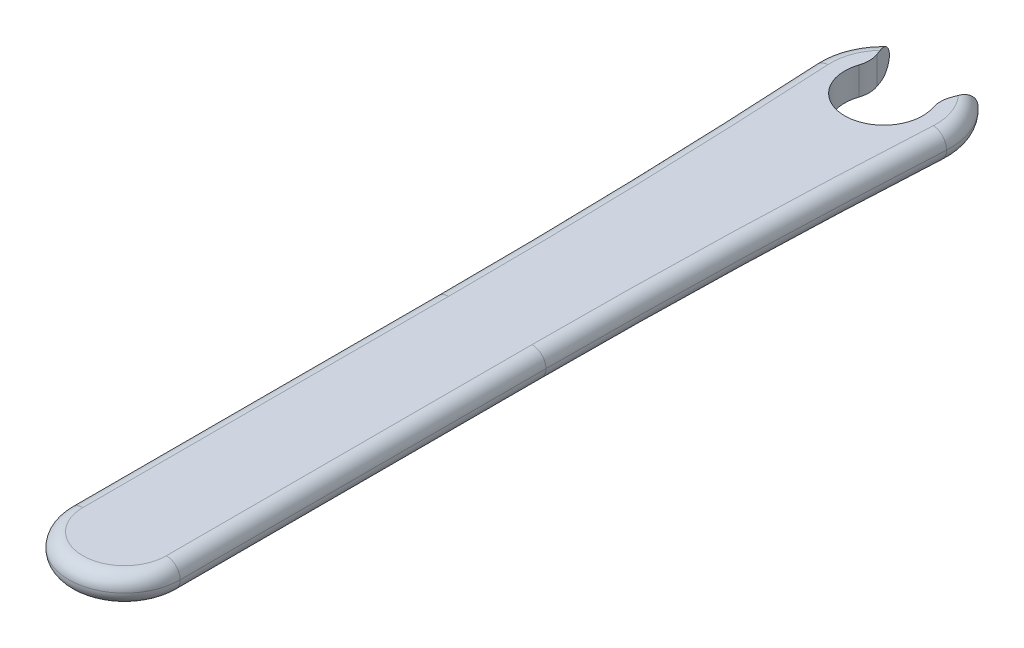
SolidWorks part; units mm, degrees
ref_plane "Front Plane" through (0, 0, 0) normal (0, 0, 1) x (1, 0, 0)
ref_plane "Top Plane" through (0, 0, 0) normal (0, 1, 0) x (1, 0, 0)
ref_plane "Right Plane" through (0, 0, 0) normal (1, 0, 0) x (0, 0, -1)
sketch "Sketch1" plane through (0, 0, 0) normal (0, 1, 0) x (1, 0, 0)
  line L0 (-20.1954, 140) -> (36203.669, 140) construction
  line L1 (-6, 140) -> (-7.9571, 145.377)
  line L2 (6, 140) -> (7.9571, 145.377)
  line L3 (0, 45.0373) -> (0, 50045.0373) construction
  line L4 (10, 65.7159) -> (10, 0)
  line L5 (-10, 65.7159) -> (-10, 0)
  line L6 (-0.087, -10) -> (49999.913, -10) construction
  arc A0 (-6, 140) -> (6, 140) centre (0, 136.3944) ccw
  arc A1 (-7.9571, 145.377) -> (7.9571, 145.377) centre (0, 136.3944) ccw
  arc A2 (-11.9808, 135.7159) -> (-10, 65.7159) centre (-1247.8657, 65.7159) cw
  arc A3 (11.9808, 135.7159) -> (10, 65.7159) centre (1247.8657, 65.7159) ccw
  arc A4 (-10, 0) -> (10, 0) centre (0, 0) ccw
  point P1 (8.161, 145.4828)
  point P22 (0, -10)
  point P23 (0, 0)
  point P24 (-115.4309, 153.3599)
  point P25 (8.161, 145.4828)
  point P26 (-4.9117, 140)
  point P27 (-5.913, 140)
  dimension "D1" = 7
  dimension "D2" = 5
  dimension "D3" = 12
  dimension "D4" = 20
  dimension "D5" = 20
  dimension "D6" = 20
  dimension "D7" = 150
  dimension "D8" = 70
extrude "Boss-Extrude1" add sketch "Sketch1" along normal blind 5 contours L5 A4 L4 A3 A1 A2 | L1 A1 L2 A0 region at (0, 0, -129.0757) region at (0, 0, -60.6272)
fillet "Fillet1" radius 2.5 14 edges at (11.0776, 0, -141.0082) (10.4953, 0, -100.7299) (10, 0, -32.8579) (0, 0, 10) (-10, 0, -32.8579) (-10.4953, 0, -100.7299) (11.0776, 5, -141.0082) (10.4953, 5, -100.7299) (10, 5, -32.8579) (0, 5, 10) (-10, 5, -32.8579) (-10.4953, 5, -100.7299) (-11.0776, 0, -141.0082) (-11.0776, 5, -141.0082)
fillet "Fillet2" radius 5 2 edges at (6, 2.5, -140) (-6, 2.5, -140)
